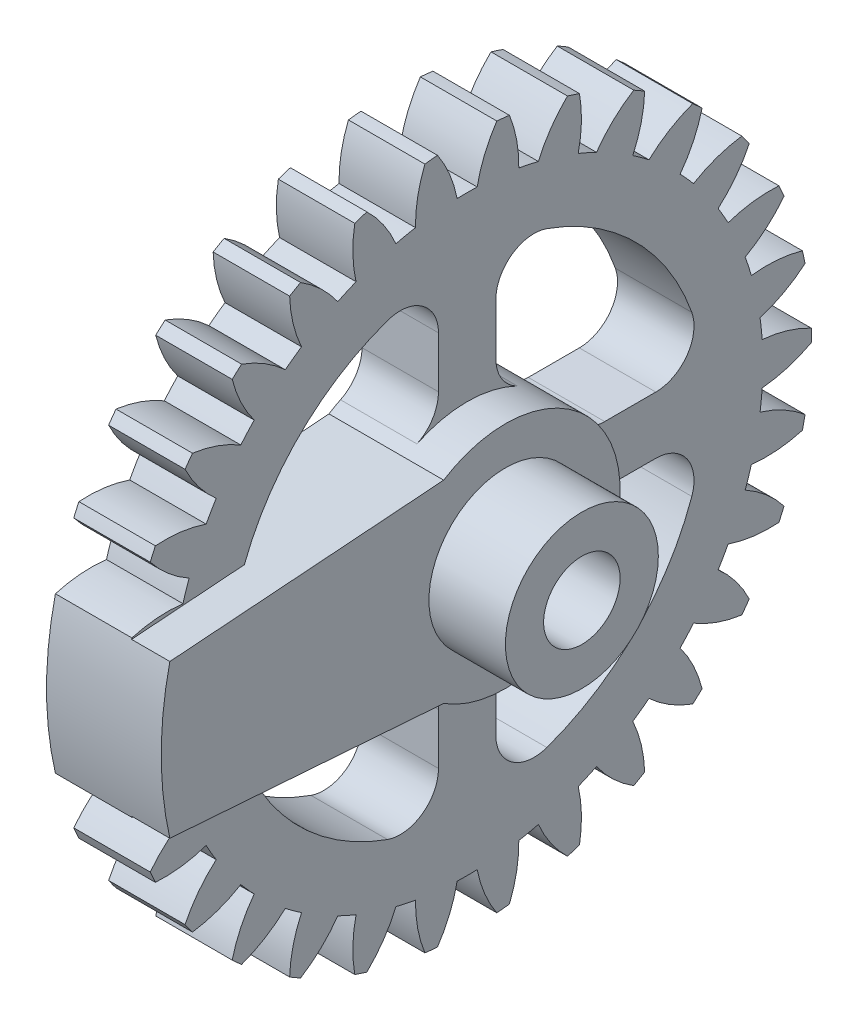
SolidWorks part; units mm, degrees
ref_plane "Plane1" through (0, 0, 0) normal (0, 0, 1) x (1, 0, 0)
ref_plane "Plane2" through (0, 0, 0) normal (0, 1, 0) x (1, 0, 0)
ref_plane "Plane3" through (0, 0, 0) normal (1, 0, 0) x (0, 0, -1)
sketch "HoldingSke" plane through (0, 0, 0) normal (0, 1, 0) x (1, 0, 0)
  line L0 (0, 0) -> (0.7698, -0.4444)
  line L1 (-15, 0) -> (100, 0) construction
  line L2 (0, 0) -> (-2.1039, 2.3779)
  line L3 (0, 0) -> (-11.863, 4.5341)
  line L4 (0, 0) -> (7.479, 4.318)
  line L5 (0, 0) -> (-46.8476, -17.4728)
  line L6 (0, 0) -> (-3.3159, -2.2372)
  line L7 (-2.1039, 2.3779) -> (8.6586, 51.2059)
  line L8 (-76.2, 54.61) -> (-74.8, 54.61)
  line L9 (-71.009, 38.7566) -> (-53.1078, 45.2721)
  line L10 (-76.2, 71.12) -> (104.1128, 71.12)
  line L11 (0, 0) -> (-4, 0)
  line L12 (-76.2, 101.6) -> (-76.158, 101.6)
  line L13 (24.9733, 27.94) -> (52.9518, 28.4284)
  line L14 (24.9733, 27.94) -> (24.9743, 27.94)
  line L15 (24.9733, 27.94) -> (100.4006, 29.5858)
  line L16 (-63.627, -1.125) -> (-12.827, -1.125)
  circle A0 centre (0, 0) radius 4
  circle A1 centre (0, 0) radius 15.4677
  circle A2 centre (0, 0) radius 37.5
  circle A3 centre (0, 0) radius 4
  dimension "MHD" = 30.9355
  dimension "Hub_dia" = 75
  dimension "Bore" = 8
  dimension "MBD" = 8
  dimension "Num_teeth" = 30
  dimension "Pitch" = 0.8889
  dimension "Overall_len" = 50
  dimension "Show_teeth" = 30
  dimension "Thickness" = 4
  dimension "OAL" = 50.0001
  dimension "T_dim" = 1.4
  dimension "Ap" = 20
  dimension "H" = 19.05
  dimension "Pitch_radius" = 180.3128
  dimension "Width" = 4
  dimension "Backlash" = 0.042
  dimension "Addendum_fac" = 1
  dimension "Dedendum_fac" = 1.25
  dimension "Clearance_fac" = 0.25
  dimension "Dedendum_add" = 0.001
  dimension "Module" = 1.125
sketch "BasProSke" plane through (0, 0, 0) normal (0, 1, 0) x (1, 0, 0)
  line L0 (-10, 0) -> (60, 0) construction
  line L1 (0, 0) -> (0, 18)
  line L2 (0, 0) -> (4, 0)
  line L3 (4, 0) -> (4, 18)
  line L4 (4, 18) -> (0, 18)
  dimension "Thickness" = 4
  dimension "Diameter" = 36
revolve "Base-Revolve" add sketch "BasProSke" angle 360 about L0
sketch "TooCutSke" plane through (0, 0, 0) normal (1, 0, 0) x (0, 0, -1)
  line L1 (0, 0) -> (0, 107) construction
  line L2 (0, 0) -> (-0.9567, 16.8479) construction
  line L3 (0, 0) -> (-3.5238, 33.5265) construction
  line L4 (-0.9567, 16.8479) -> (-1.7619, 16.7632) construction
  arc A0 (0.5235, 15.4589) -> (-0.5235, 15.4589) centre (0, 0) ccw
  arc A1 (1.5687, 17.957) -> (-1.5687, 17.957) centre (0, 0) ccw
  circle A2 centre (0, 0) radius 16.875 construction
  circle A3 centre (0, 0) radius 15.8573 construction
  arc A4 (-0.5235, 15.4589) -> (-1.5687, 17.957) centre (-7.1465, 14.1556) ccw
  arc A5 (1.5687, 17.957) -> (0.5235, 15.4589) centre (7.1465, 14.1556) ccw
  dimension "Root_dia" = 30.9355
  dimension "Overcut_dia" = 36.0508
  dimension "Pitch_dia" = 33.75
  dimension "Base_dia" = 31.7146
  dimension "Flank_rad" = 6.75
  dimension "Half_ang" = 6
  dimension "Half_CT" = 0.8097
extrude "ToothCut" cut sketch "TooCutSke" along normal through all
fillet "Breaks" [suppressed] radius 0.0225 tangent propagation no
fillet "RootFillets" [suppressed] radius 0.2823
pattern_circular "TeethCuts" count 30 every 12 about axis through (-10, 0, 0) along (1, 0, 0) of "ToothCut", "RootFillets", "Breaks"
sketch "HubNeaOneSke" plane through (0, 0, 0) normal (-1, 0, 0) x (0, 0, 1)
  circle A0 centre (0, 0) radius 15.4677
  dimension "Diameter" = 30.9355
extrude "HubNearOne" [suppressed] add sketch "HubNeaOneSke" along normal blind 46.0001
sketch "HubNeaBotSke" plane through (0, 0, 0) normal (-1, 0, 0) x (0, 0, 1)
  circle A0 centre (0, 0) radius 15.4677
  dimension "Diameter" = 30.9355
extrude "HubNearBoth" [suppressed] add sketch "HubNeaBotSke" along normal blind 23
ref_plane "FarPln" through (4, 0, 0) normal (1, 0, 0) x (0, 0, -1)
sketch "HubFarSke" plane through (4, 0, 0) normal (1, 0, 0) x (0, 0, -1)
  circle A0 centre (0, 0) radius 15.4677
  dimension "Diameter" = 30.9355
extrude "HubFar" [suppressed] add sketch "HubFarSke" along normal blind 23
sketch "BorSke" plane through (0, 0, 0) normal (1, 0, 0) x (0, 0, -1)
  circle A0 centre (0, 0) radius 4
  dimension "Diameter" = 8
extrude "Bore" cut sketch "BorSke" along normal mid plane 100.0001
sketch "KeySke" plane through (0, 0, 0) normal (1, 0, 0) x (0, 0, -1)
  line L0 (-1.5, 0) -> (-1.5, 5.4)
  line L1 (-1.5, 5.4) -> (1.5, 5.4)
  line L2 (1.5, 5.4) -> (1.5, 0)
  line L3 (0, 0) -> (0, 34) construction
  line L4 (-1.5, 0) -> (1.5, 0)
  dimension "Offset" = 5.4
  dimension "Width" = 3
extrude "Keyway" [suppressed] cut sketch "KeySke" along normal mid plane 100.0001
pattern_circular "Keyway2" [suppressed] count 2 every 90 about axis through (-10, 0, 0) along (1, 0, 0) reverse direction yes
sketch "Sketch1" plane through (4, 0, 0) normal (1, 0, 0) x (0, 0, -1)
  line L0 (0, 0) -> (-14.05, 0) construction
  line L1 (-14.1968, 1.9946) -> (-1.8657, 2.902) construction
  line L2 (-1.8657, -2.902) -> (-14.1968, -1.9946) construction
  line L3 (-14.2151, 2.2439) -> (-1.9463, 3.1467)
  line L4 (-1.9463, -3.1467) -> (-14.2151, -2.2439)
  arc A0 (-1.8657, -2.902) -> (-1.8657, 2.902) centre (0, 0) ccw construction
  arc A1 (-14.1968, 1.9946) -> (-14.1968, -1.9946) centre (-14.05, 0) ccw construction
  arc A2 (-1.9463, -3.1467) -> (-1.9463, 3.1467) centre (0, 0) ccw
  arc A3 (-14.2151, 2.2439) -> (-14.2151, -2.2439) centre (-14.05, 0) ccw
  dimension "D2" = 2
  dimension "D3" = 3.45
  dimension "D1" = 14.05
  dimension "D4" = 12.331
  dimension "D5" = 0.25
sketch "Sketch4" plane through (4, 0, 0) normal (1, 0, 0) x (0, 0, -1)
  line L0 (-3.2277, 5.0578) -> (-17.549, 4.004)
  line L1 (-3.2277, -5.0578) -> (-17.549, -4.004)
  line L2 (-14.2151, 2.2439) -> (-1.9463, 3.1467) construction
  line L3 (-1.9463, -3.1467) -> (-14.2151, -2.2439) construction
  line L4 (0, 0) -> (-22.7741, 0) construction
  arc A0 (-3.2277, -5.0578) -> (-3.2277, 5.0578) centre (0, 0) ccw
  arc A2 (-17.549, 4.004) -> (-17.549, -4.004) centre (0, 0) ccw
  dimension "D1" = 6
  dimension "D2" = 2
extrude "Boss-Extrude1" add sketch "Sketch4" along normal blind 2 and the other way up to surface (4 mm away) other way up to face at (0, 0, -4)
extrude "Cut-Extrude2" cut sketch "Sketch1" against normal up to next
sketch "Sketch6" plane through (4, 0, 0) normal (1, 0, 0) x (0, 0, -1)
  circle A0 centre (0, 0) radius 4
  circle A1 centre (0, 0) radius 2 construction
  dimension "D1" = 8
  dimension "D2" = 2
extrude "Boss-Extrude2" add sketch "Sketch6" along normal blind 4 from surface starting at face at (6, 0, 8.1942)
sketch "Sketch7" plane through (10, 0, 0) normal (1, 0, 0) x (0, 0, -1)
  line L0 (-1.5, 5.8095) -> (-1.5, 12.3772)
  line L1 (1.5, 5.8095) -> (1.5, 12.3772)
  line L2 (1.5, -5.8095) -> (1.5, -12.3772)
  line L3 (-1.5, -5.8095) -> (-1.5, -12.3772)
  line L4 (5.8095, 1.5) -> (12.3772, 1.5)
  line L5 (0, 0) -> (0, 12.4677) construction
  line L6 (0, 0) -> (12.4677, 0) construction
  line L11 (0, 0) -> (0, -12.4677) construction
  line L12 (5.8095, -1.5) -> (12.3772, -1.5)
  line L13 (-17.549, -4.004) -> (-3.2277, -5.0578) construction
  line L14 (-3.2277, 5.0578) -> (-17.549, 4.004) construction
  line L15 (-11.6511, -4.438) -> (-3.2277, -5.0578)
  line L16 (-3.2277, 5.0578) -> (-11.6511, 4.438)
  circle A0 centre (0, 0) radius 2 construction
  circle A1 centre (0, 0) radius 2
  circle A2 centre (0, 0) radius 15.4677 construction
  arc A4 (-3.2277, -5.0578) -> (-1.5, -5.8095) centre (0, 0) ccw
  arc A5 (-3.2277, -5.0578) -> (-3.2277, 5.0578) centre (0, 0) ccw construction
  arc A6 (-1.5, 12.3772) -> (-11.6511, 4.438) centre (0, 0) ccw
  arc A9 (-11.6511, -4.438) -> (-1.5, -12.3772) centre (0, 0) ccw
  arc A11 (-1.5, 5.8095) -> (-3.2277, 5.0578) centre (0, 0) ccw
  arc A12 (5.8095, 1.5) -> (1.5, 5.8095) centre (0, 0) ccw
  arc A13 (12.3772, 1.5) -> (1.5, 12.3772) centre (0, 0) ccw
  arc A14 (1.5, -5.8095) -> (5.8095, -1.5) centre (0, 0) ccw
  arc A15 (1.5, -12.3772) -> (12.3772, -1.5) centre (0, 0) ccw
  dimension "D3" = 3
  dimension "D4" = 3
extrude "Cut-Extrude3" cut sketch "Sketch7" against normal through all
fillet "Fillet1" radius 2 12 edges at (2, -12.3772, -1.5) (2, -12.3772, 1.5) (2, -5.8095, 1.5) (2, -1.5, -12.3772) (2, -1.5, -5.8095) (2, -5.8095, -1.5) (2, 1.5, -12.3772) (2, 1.5, -5.8095) (2, 12.3772, -1.5) (2, 5.8095, -1.5) (2, 5.8095, 1.5) (2, 12.3772, 1.5)
equation "' \"Module@HoldingSke\" = 6.35"
equation "' \"Num_teeth@HoldingSke\" = 12"
equation "' \"Ap@HoldingSke\" =  20"
equation "' \"Ap@HoldingSke\" = 20"
equation "' \"Width@HoldingSke\" = 0.5 * 25.4"
equation "' \"Hub_dia@HoldingSke\"= 1 * 25.4"
equation "' \"Hub_dia@HoldingSke\" = 1 * 25.4"
equation "' \"Overall_len@HoldingSke\" = 1.0 * 25.4"
equation "' \"Bore@HoldingSke\" = 0.75 * 25.4"
equation "' \"T_dim@HoldingSke\" = 0.1 * 25.4"
equation "' \"Width@KeySke\" = 0.25 * 25.4"
equation "' \"Show_teeth@HoldingSke\" = 13"
equation "' \"Backlash@HoldingSke\" = 0.009 * 25.4"
equation "' \"Addendum_fac@HoldingSke\" = 1.0"
equation "' \"Dedendum_fac@HoldingSke\" = 1.25"
equation "' \"Dedendum_add@HoldingSke\" = 0.00005 * 25.4"
equation "' \"Clearance_fac@HoldingSke\" = 0.25"
equation "\"Pitch@HoldingSke\" = 1 / \"Module@HoldingSke\""
equation "\"Overcut_dia@TooCutSke\" = (\"Num_teeth@HoldingSke\" + 2 * \"Addendum_fac@HoldingSke\") / \"Pitch@HoldingSke\" + 0.002 * 25.4"
equation "\"Pitch_dia@TooCutSke\" = \"Num_teeth@HoldingSke\" / \"Pitch@HoldingSke\""
equation "\"Base_dia@TooCutSke\" = \"Num_teeth@HoldingSke\" / \"Pitch@HoldingSke\" * cos((\"Ap@HoldingSke\"  * 3.14159265 / 180))"
equation "\"Root_dia@TooCutSke\" = (\"Num_teeth@HoldingSke\" + 2) / \"Pitch@HoldingSke\" - 2 * (\"Addendum_fac@HoldingSke\" + \"Dedendum_fac@HoldingSke\") / \"Pitch@HoldingSke\" - \"Dedendum_add@HoldingSke\" * 2"
equation "\"Half_ang@TooCutSke\" = 180 / \"Num_teeth@HoldingSke\""
equation "\"Half_CT@TooCutSke\" = \"Num_teeth@HoldingSke\" / \"Pitch@HoldingSke\" * sin((3.14159265 / 2 / \"Num_teeth@HoldingSke\")) / 2 - 7 * \"Backlash@HoldingSke\" / 4"
equation "\"Flank_rad@TooCutSke\" = \"Num_teeth@HoldingSke\" / \"Pitch@HoldingSke\" / 5"
equation "\"Radius@RootFillets\" = \"Clearance_fac@HoldingSke\" / \"Pitch@HoldingSke\" + \"Dedendum_add@HoldingSke\""
equation "\"Break_rad@Breaks\" = 0.02 / \"Pitch@HoldingSke\""
equation "\"Thickness@HoldingSke\" = \"Width@HoldingSke\""
equation "\"OAL@HoldingSke\" = \"Thickness@HoldingSke\""
equation "\"MHD@HoldingSke\" = (\"Num_teeth@HoldingSke\" + 2) / \"Pitch@HoldingSke\" - 2 * (\"Addendum_fac@HoldingSke\" + \"Dedendum_fac@HoldingSke\")  / \"Pitch@HoldingSke\" - \"Dedendum_add@HoldingSke\" * 2"
equation "\"MBD@HoldingSke\" = (\"Num_teeth@HoldingSke\" + 2) / \"Pitch@HoldingSke\" - 2 * (\"Addendum_fac@HoldingSke\" + \"Dedendum_fac@HoldingSke\")  / \"Pitch@HoldingSke\" - \"Dedendum_add@HoldingSke\" * 2 - 0.002 * 25.4"
equation "\"MHD@HoldingSke\" = ((sgn( \"MHD@HoldingSke\" - \"Hub_dia@HoldingSke\" )-1)*( \"MHD@HoldingSke\" - \"Hub_dia@HoldingSke\" ))/-2+ \"Hub_dia@HoldingSke\""
equation "\"MBD@HoldingSke\" = ((sgn( \"MBD@HoldingSke\" - \"Bore@HoldingSke\" )-1)*( \"MBD@HoldingSke\" - \"Bore@HoldingSke\" ))/-2+ \"Bore@HoldingSke\""
equation "\"OAL@HoldingSke\" = ((sgn( \"OAL@HoldingSke\" - \"Overall_len@HoldingSke\" )+1)*( \"OAL@HoldingSke\" - \"Overall_len@HoldingSke\" ))/2 + \"Overall_len@HoldingSke\" + 0.000002 * 25.4"
equation "\"Num_teeth@TeethCuts\" = int( \"Show_teeth@HoldingSke\" ) + 1"
equation "\"Num_teeth@TeethCuts\" = ((sgn( \"Num_teeth@TeethCuts\" - \"Num_teeth@HoldingSke\" )-1)*( \"Num_teeth@TeethCuts\" - \"Num_teeth@HoldingSke\" ))/-2+ \"Num_teeth@HoldingSke\""
equation "\"Num_teeth@TeethCuts\" = ((sgn( \"Num_teeth@TeethCuts\" - 2.0)+1)*( \"Num_teeth@TeethCuts\" - 2.0))/2 +2.0"
equation "\"Angle@TeethCuts\" = 360.0 / \"Num_teeth@HoldingSke\""
equation "\"Diameter@BasProSke\" = (\"Num_teeth@HoldingSke\" + 2 * \"Addendum_fac@HoldingSke\") / \"Pitch@HoldingSke\""
equation "\"Thickness@BasProSke\"  = \"Thickness@HoldingSke\""
equation "' \"Fillet_rad@BasProSke\" =  \"Thickness@HoldingSke\" * 0.05"
equation "' \"Fillet_rad@BasProSke\" = \"Thickness@HoldingSke\" * 0.05"
equation "\"MHD@HoldingSke\" = ((sgn( \"MHD@HoldingSke\" - \"Root_dia@TooCutSke\" )-1)*( \"MHD@HoldingSke\" - \"Root_dia@TooCutSke\" ))/-2+ \"Root_dia@TooCutSke\""
equation "\"Diameter@HubNeaOneSke\" = \"MHD@HoldingSke\""
equation "\"Length@HubNearOne\" = \"OAL@HoldingSke\" - \"Thickness@BasProSke\""
equation "\"Diameter@HubNeaBotSke\" = \"MHD@HoldingSke\""
equation "\"Length@HubNearBoth\" = ( \"OAL@HoldingSke\" - \"Thickness@BasProSke\" ) / 2.0"
equation "\"Thickness@FarPln\" = \"Thickness@BasProSke\""
equation "\"Diameter@HubFarSke\" = \"MHD@HoldingSke\""
equation "\"Length@HubFar\" = ( \"OAL@HoldingSke\" - \"Thickness@BasProSke\" ) / 2.0"
equation "\"Diameter@BorSke\" = \"MBD@HoldingSke\""
equation "\"D1@Bore\" = \"OAL@HoldingSke\" * 2.0"
equation "\"D1@Keyway\" = \"OAL@HoldingSke\" * 2.0"
equation "\"Offset@KeySke\" = \"T_dim@HoldingSke\" + \"MBD@HoldingSke\" / 2.0"
